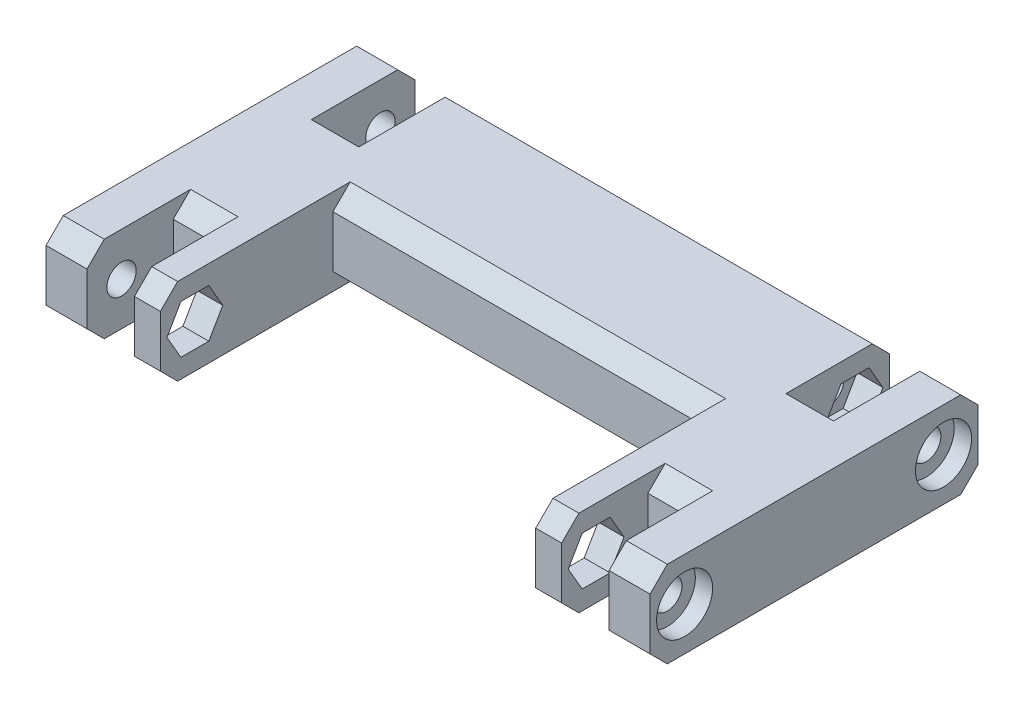
SolidWorks part; units mm, degrees
ref_plane "Front Plane" through (0, 0, 0) normal (0, 0, 1) x (1, 0, 0)
ref_plane "Top Plane" through (0, 0, 0) normal (0, 1, 0) x (1, 0, 0)
ref_plane "Right Plane" through (0, 0, 0) normal (1, 0, 0) x (0, 0, -1)
sketch "Sketch1" plane through (0, 0, 0) normal (0, 1, 0) x (1, 0, 0)
  line L1 (-35, -19) -> (35, -19)
  line L2 (-35, -19) -> (-35, 19)
  line L3 (-35, 19) -> (35, 19)
  line L4 (35, -19) -> (35, 19)
  line L5 (-35, -19) -> (35, 19) construction
  line L6 (-35, 19) -> (35, -19) construction
  point P0 (0, 0)
  dimension "D1" = 70
  dimension "D2" = 38
extrude "Boss-Extrude1" add sketch "Sketch1" along normal blind 10
sketch "Sketch2" plane through (0, 10, 0) normal (0, 1, 0) x (1, 0, 0)
  line L0 (35, 19) -> (-35, 19) construction
  line L1 (-30.25, 19) -> (-24.75, 19)
  line L2 (-30.25, 19) -> (-30.25, 9)
  line L3 (-30.25, 9) -> (-24.75, 9)
  line L4 (-24.75, 19) -> (-24.75, 9)
  line L5 (0, 0) -> (0, 19) construction
  line L6 (24.75, 19) -> (24.75, 9)
  line L7 (30.25, 9) -> (24.75, 9)
  line L8 (30.25, 19) -> (30.25, 9)
  line L9 (30.25, 19) -> (24.75, 19)
  dimension "D1" = 5.5
  dimension "D2" = 10
  dimension "D3" = 49.5
extrude "Cut-Extrude1" cut sketch "Sketch2" against normal through all
hole_wizard "CBORE for M3 Cheese Head Screw1" positions "Sketch7" profile "Sketch8" counterbore size "M3" standard "ISO"
sketch "Sketch7" plane through (35, 0, 0) normal (1, 0, 0) x (0, 0, -1)
  line L0 (-19, 10) -> (19, 10) construction
  line L1 (19, 10) -> (19, 0) construction
  point P0 (15, 5)
  dimension "D1" = 5
  dimension "D2" = 4
sketch "Sketch8" plane through (35, 5, -15) normal (0, 1, 0) x (0, 0, -1)
  line L0 (0, 0) -> (0, 16.0215)
  line L1 (0, 16.0215) -> (1.7, 15)
  line L2 (1.7, 15) -> (1.7, 2)
  line L3 (1.7, 2) -> (3.25, 2)
  line L4 (3.25, 2) -> (3.25, 0)
  line L5 (3.25, 0) -> (0, 0)
  line L10 (0, 16.0215) -> (-1.7, 15) construction
  line L11 (0, -6.35) -> (0, 107.95) construction
  dimension "Hole Dia." = 3.4
  dimension "Hole Depth" = 15
  dimension "C'Bore Dia." = 6.5
  dimension "C'Bore Depth" = 2
  dimension "Drill Angle" = 118
sketch "Sketch9" plane through (24.75, 0, 0) normal (1, 0, 0) x (0, 0, -1)
  line L1 (16.6166, 7.8) -> (13.3834, 7.8)
  line L2 (13.3834, 7.8) -> (11.7668, 5)
  line L3 (11.7668, 5) -> (13.3834, 2.2)
  line L4 (13.3834, 2.2) -> (16.6166, 2.2)
  line L5 (16.6166, 2.2) -> (18.2332, 5)
  line L6 (18.2332, 5) -> (16.6166, 7.8)
  circle A0 centre (15, 5) radius 2.8 construction
  dimension "D1" = 5.6
extrude "Cut-Extrude2" cut sketch "Sketch9" against normal blind 3
mirror "Mirror1" about plane through (0, 0, 0) normal (1, 0, 0) of "Cut-Extrude2", "CBORE for M3 Cheese Head Screw1"
mirror "Mirror2" about plane through (0, 0, 0) normal (0, 0, 1) of "Cut-Extrude1", "CBORE for M3 Cheese Head Screw1", "Cut-Extrude2", "Mirror1"
chamfer "Chamfer1" distance 2 angle 45 12 edges at (32.625, 0, -19) (32.625, 10, -19) (0, 0, -19) (0, 10, -19) (-32.625, 0, -19) (-32.625, 10, -19) (-32.625, 0, 19) (32.625, 0, 19) (0, 0, 19) (32.625, 10, 19) (-32.625, 10, 19) (0, 10, 19)
sketch "Sketch10" plane through (0, 10, 0) normal (0, 1, 0) x (1, 0, 0)
  line L0 (0, 0) -> (0, -19) construction
  line L1 (24.75, -19) -> (-24.75, -19) construction
  line L2 (-24.75, -9) -> (-24.75, -17) construction
  line L3 (-21.75, -19) -> (21.75, -19)
  line L4 (-21.75, -19) -> (-21.75, 1)
  line L5 (-21.75, 1) -> (21.75, 1)
  line L6 (21.75, -19) -> (21.75, 1)
  line L7 (-21.75, -19) -> (21.75, 1) construction
  line L8 (-21.75, 1) -> (21.75, -19) construction
  point P5 (0, -9)
  dimension "D1" = 3
  dimension "D2" = 20
extrude "Cut-Extrude3" cut sketch "Sketch10" against normal through all
chamfer "Chamfer2" distance 2 angle 45 2 edges at (0, 0, -1) (0, 10, -1)
chamfer "Chamfer3" distance 2 angle 45 8 edges at (27.5, 0, -9) (27.5, 10, -9) (27.5, 10, 9) (27.5, 0, 9) (-27.5, 10, 9) (-27.5, 0, 9) (-27.5, 0, -9) (-27.5, 10, -9)
